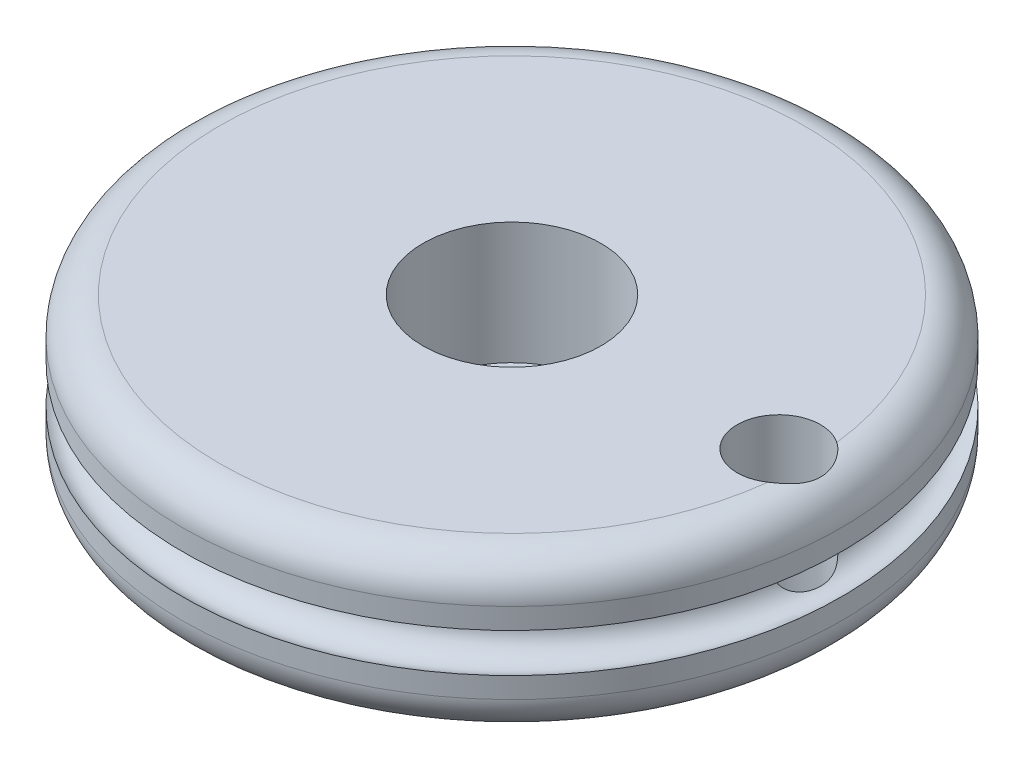
SolidWorks part; units mm, degrees
ref_plane "Front Plane" through (0, 0, 0) normal (0, 0, 1) x (1, 0, 0)
ref_plane "Top Plane" through (0, 0, 0) normal (0, 1, 0) x (1, 0, 0)
ref_plane "Right Plane" through (0, 0, 0) normal (1, 0, 0) x (0, 0, -1)
sketch "Sketch1" plane through (0, 0, 0) normal (0, 1, 0) x (1, 0, 0)
  line L1 (0, 0) -> (8.89, 0) construction
  circle A0 centre (0, 0) radius 8.89
  circle A1 centre (0, 0) radius 0.9
  circle A3 centre (7.2, 0) radius 1.125
  dimension "D1" = 17.78
  dimension "D2" = 1.8
  dimension "D3" = 2.25
  dimension "D4" = 7.2
extrude "Boss-Extrude1" add sketch "Sketch1" along normal blind 4.175
ref_plane "Plane1" through (0, 2.0875, 0) normal (0, -1, 0) x (-1, 0, 0)
sketch "Sketch3" plane through (0, 2.0875, 0) normal (0, -1, 0) x (-1, 0, 0)
  circle A0 centre (0, 0) radius 8.5725
  dimension "D1" = 17.145
sketch "Sketch2" plane through (0, 4.175, 0) normal (0, 1, 0) x (1, 0, 0)
  circle A0 centre (0, 0) radius 2.4
  dimension "D1" = 4.8
extrude "Cut-Extrude1" cut sketch "Sketch2" against normal blind 3.286
sweep "Cut-Sweep1" cut path "Sketch3" circular profile diameter 1.23 parameters "D3"=1.23
fillet "Fillet1" radius 1 2 edges at (0, 0, 8.89) (0, 4.175, 8.89)
